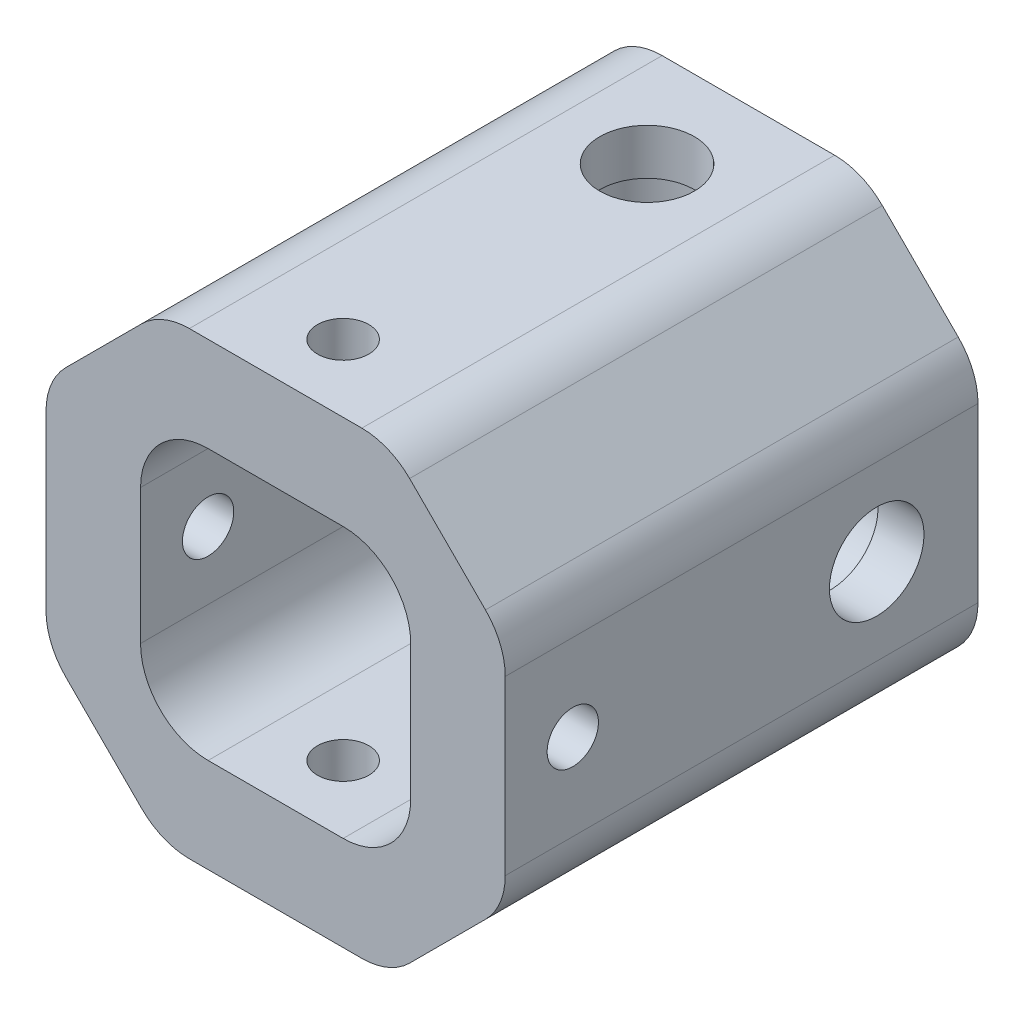
SolidWorks part; units mm, degrees
ref_plane "正面" through (0, 0, 0) normal (0, 0, 1) x (1, 0, 0)
ref_plane "平面" through (0, 0, 0) normal (0, 1, 0) x (1, 0, 0)
ref_plane "右側面" through (0, 0, 0) normal (1, 0, 0) x (0, 0, -1)
sketch "ｽｹｯﾁ1" plane through (0, 0, 0) normal (0, 0, 1) x (1, 0, 0)
  line L0 (7.4558, -18) -> (18, -7.4558)
  line L1 (-18, 7.4558) -> (-18, -7.4558)
  line L2 (-18, -7.4558) -> (-7.4558, -18)
  line L3 (-7.4558, -18) -> (7.4558, -18)
  line L4 (18, -7.4558) -> (18, 7.4558)
  line L5 (18, 7.4558) -> (7.4558, 18)
  line L6 (7.4558, 18) -> (-7.4558, 18)
  line L7 (-7.4558, 18) -> (-18, 7.4558)
  circle A0 centre (0, 0) radius 18 construction
  point P1 (0, -18)
  point P12 (-18, 0)
  dimension "D1" = 18
extrude "ﾎﾞｽ - 押し出し1" add sketch "ｽｹｯﾁ1" along normal mid plane 15
sketch "ｽｹｯﾁ2" plane through (0, 0, 7.5) normal (0, 0, 1) x (1, 0, 0)
  line L0 (7.4558, 18) -> (-7.4558, 18) construction
  line L1 (10, -10) -> (-10, -10)
  line L2 (10, -10) -> (10, 10)
  line L3 (10, 10) -> (-10, 10)
  line L4 (-10, -10) -> (-10, 10)
  line L5 (10, -10) -> (-10, 10) construction
  line L6 (10, 10) -> (-10, -10) construction
  line L7 (18, -7.4558) -> (18, 7.4558) construction
  point P0 (0, 0)
  dimension "D1" = 8
  dimension "D2" = 8
extrude "ｶｯﾄ - 押し出し1" cut sketch "ｽｹｯﾁ2" against normal through all both and the other way through all
sketch "ｽｹｯﾁ11" plane through (0, 18, 0) normal (0, 1, 0) x (1, 0, 0)
  line L1 (-14.7524, -23.747) -> (14.7524, -23.747)
  line L2 (-14.7524, -23.747) -> (-14.7524, 23.747)
  line L3 (-14.7524, 23.747) -> (14.7524, 23.747)
  line L4 (14.7524, -23.747) -> (14.7524, 23.747)
  line L5 (-14.7524, -23.747) -> (14.7524, 23.747) construction
  line L6 (-14.7524, 23.747) -> (14.7524, -23.747) construction
  point P0 (0, 0)
extrude "ｶｯﾄ - 押し出し7" cut sketch "ｽｹｯﾁ11" against normal blind 1
mirror "ﾐﾗｰ1" about plane through (0, 0, 0) normal (0, 1, 0) of "ｶｯﾄ - 押し出し7"
sketch "ｽｹｯﾁ12" plane through (-18, 0, 0) normal (-1, 0, 0) x (0, 0, 1)
  line L1 (-10.119, -12.8597) -> (10.119, -12.8597)
  line L2 (-10.119, -12.8597) -> (-10.119, 12.8597)
  line L3 (-10.119, 12.8597) -> (10.119, 12.8597)
  line L4 (10.119, -12.8597) -> (10.119, 12.8597)
  line L5 (-10.119, -12.8597) -> (10.119, 12.8597) construction
  line L6 (-10.119, 12.8597) -> (10.119, -12.8597) construction
  point P0 (0, 0)
extrude "ｶｯﾄ - 押し出し8" cut sketch "ｽｹｯﾁ12" against normal blind 1
mirror "ﾐﾗｰ2" about plane through (0, 0, 0) normal (1, 0, 0) of "ｶｯﾄ - 押し出し8"
fillet "ﾌｨﾚｯﾄ1" radius 5 4 edges at (10, -10, 0) (-10, -10, 0) (10, 10, 0) (-10, 10, 0)
fillet "ﾌｨﾚｯﾄ2" radius 5 8 edges at (17, -8.4558, 0) (8.4558, -17, 0) (-8.4558, -17, 0) (17, 8.4558, 0) (-17, -8.4558, 0) (-17, 8.4558, 0) (8.4558, 17, 0) (-8.4558, 17, 0)
sketch "ｽｹｯﾁ3" plane through (0, -17, 0) normal (0, -1, 0) x (1, 0, 0)
  circle A0 centre (0, 0) radius 4.2
  dimension "D1" = 8.4
extrude "ｶｯﾄ - 押し出し2" cut sketch "ｽｹｯﾁ3" against normal through all both and the other way through all
sketch "ｽｹｯﾁ4" plane through (17, 0, 0) normal (1, 0, 0) x (0, 0, -1)
  circle A0 centre (0, 0) radius 4.2
  dimension "D1" = 8.4
extrude "ｶｯﾄ - 押し出し3" cut sketch "ｽｹｯﾁ4" against normal through all both and the other way through all
sketch "ｽｹｯﾁ5" plane through (0, 0, 7.5) normal (0, 0, 1) x (1, 0, 0)
  line L0 (5, 10) -> (-5, 10) construction
  line L1 (10, -5) -> (10, 5) construction
  line L2 (-5, -10) -> (5, -10) construction
  line L3 (-10, 5) -> (-10, -5) construction
  line L4 (5, 10) -> (-5, 10)
  line L5 (10, -5) -> (10, 5)
  line L6 (-5, -10) -> (5, -10)
  line L7 (-10, 5) -> (-10, -5)
  line L8 (9.9203, -15.5355) -> (15.5355, -9.9203)
  line L9 (17, -6.3848) -> (17, 6.3848)
  line L10 (15.5355, 9.9203) -> (9.9203, 15.5355)
  line L11 (17, -6.3848) -> (17, 6.3848)
  line L12 (-9.9203, 15.5355) -> (-15.5355, 9.9203)
  line L13 (6.3848, 17) -> (-6.3848, 17)
  line L14 (-15.5355, -9.9203) -> (-9.9203, -15.5355)
  line L15 (6.3848, 17) -> (-6.3848, 17)
  line L16 (9.9203, -15.5355) -> (15.5355, -9.9203)
  line L18 (15.5355, 9.9203) -> (9.9203, 15.5355)
  line L20 (-9.9203, 15.5355) -> (-15.5355, 9.9203)
  line L22 (-15.5355, -9.9203) -> (-9.9203, -15.5355)
  line L32 (-17, 6.3848) -> (-17, -6.3848)
  line L33 (-17, 6.3848) -> (-17, -6.3848)
  line L34 (-6.3848, -17) -> (6.3848, -17)
  line L35 (-6.3848, -17) -> (6.3848, -17)
  arc A0 (-5, 10) -> (-10, 5) centre (-5, 5) ccw construction
  arc A1 (-5, 10) -> (-10, 5) centre (-5, 5) ccw
  arc A2 (10, 5) -> (5, 10) centre (5, 5) ccw construction
  arc A3 (5, -10) -> (10, -5) centre (5, -5) ccw construction
  arc A4 (-10, -5) -> (-5, -10) centre (-5, -5) ccw construction
  arc A5 (10, 5) -> (5, 10) centre (5, 5) ccw
  arc A6 (5, -10) -> (10, -5) centre (5, -5) ccw
  arc A7 (-10, -5) -> (-5, -10) centre (-5, -5) ccw
  arc A24 (15.5355, -9.9203) -> (17, -6.3848) centre (12, -6.3848) ccw
  arc A25 (15.5355, -9.9203) -> (17, -6.3848) centre (12, -6.3848) ccw
  arc A26 (17, 6.3848) -> (15.5355, 9.9203) centre (12, 6.3848) ccw
  arc A27 (17, 6.3848) -> (15.5355, 9.9203) centre (12, 6.3848) ccw
  arc A28 (9.9203, 15.5355) -> (6.3848, 17) centre (6.3848, 12) ccw
  arc A29 (9.9203, 15.5355) -> (6.3848, 17) centre (6.3848, 12) ccw
  arc A30 (-6.3848, 17) -> (-9.9203, 15.5355) centre (-6.3848, 12) ccw
  arc A31 (-6.3848, 17) -> (-9.9203, 15.5355) centre (-6.3848, 12) ccw
  arc A32 (-15.5355, 9.9203) -> (-17, 6.3848) centre (-12, 6.3848) ccw
  arc A33 (-15.5355, 9.9203) -> (-17, 6.3848) centre (-12, 6.3848) ccw
  arc A34 (-17, -6.3848) -> (-15.5355, -9.9203) centre (-12, -6.3848) ccw
  arc A35 (-17, -6.3848) -> (-15.5355, -9.9203) centre (-12, -6.3848) ccw
  arc A36 (-9.9203, -15.5355) -> (-6.3848, -17) centre (-6.3848, -12) ccw
  arc A37 (-9.9203, -15.5355) -> (-6.3848, -17) centre (-6.3848, -12) ccw
  arc A38 (6.3848, -17) -> (9.9203, -15.5355) centre (6.3848, -12) ccw
  arc A39 (6.3848, -17) -> (9.9203, -15.5355) centre (6.3848, -12) ccw
  dimension "D1" = 0
extrude "ﾎﾞｽ - 押し出し2" add sketch "ｽｹｯﾁ5" along normal blind 20
sketch "ｽｹｯﾁ6" plane through (0, -17, 0) normal (0, -1, 0) x (1, 0, 0)
  circle A1 centre (0, 0) radius 4.2
  circle A2 centre (0, 0) radius 3.5
  circle A3 centre (0, 0) radius 4.2 construction
  dimension "D1" = 7
extrude "ﾎﾞｽ - 押し出し3" add sketch "ｽｹｯﾁ6" against normal blind 3.4
mirror "ﾐﾗｰ3" about plane through (0, 0, 0) normal (0, 1, 0) of "ﾎﾞｽ - 押し出し3"
sketch "ｽｹｯﾁ13" plane through (-17, 0, 0) normal (-1, 0, 0) x (0, 0, 1)
  circle A0 centre (0, 0) radius 4.2 construction
  circle A1 centre (0, 0) radius 4.2
  circle A2 centre (0, 0) radius 3.5
  dimension "D1" = 7
extrude "ﾎﾞｽ - 押し出し4" add sketch "ｽｹｯﾁ13" along direction (-1, 0, 0) on the side against the normal blind 3.4
mirror "ﾐﾗｰ4" about plane through (0, 0, 0) normal (1, 0, 0) of "ﾎﾞｽ - 押し出し4"
sketch "ｽｹｯﾁ14" plane through (-17, 0, 0) normal (-1, 0, 0) x (0, 0, 1)
  line L0 (27.5, 6.3848) -> (27.5, -6.3848) construction
  circle A0 centre (22.5, 0) radius 1.9
  dimension "D1" = 3.8
  dimension "D2" = 5
extrude "ｶｯﾄ - 押し出し9" cut sketch "ｽｹｯﾁ14" against normal through all
sketch "ｽｹｯﾁ15" plane through (0, -17, 0) normal (0, -1, 0) x (1, 0, 0)
  line L0 (-6.3848, 27.5) -> (6.3848, 27.5) construction
  circle A0 centre (0, 22.5) radius 1.9
  dimension "D1" = 3.8
  dimension "D2" = 5
extrude "ｶｯﾄ - 押し出し10" cut sketch "ｽｹｯﾁ15" against normal through all
